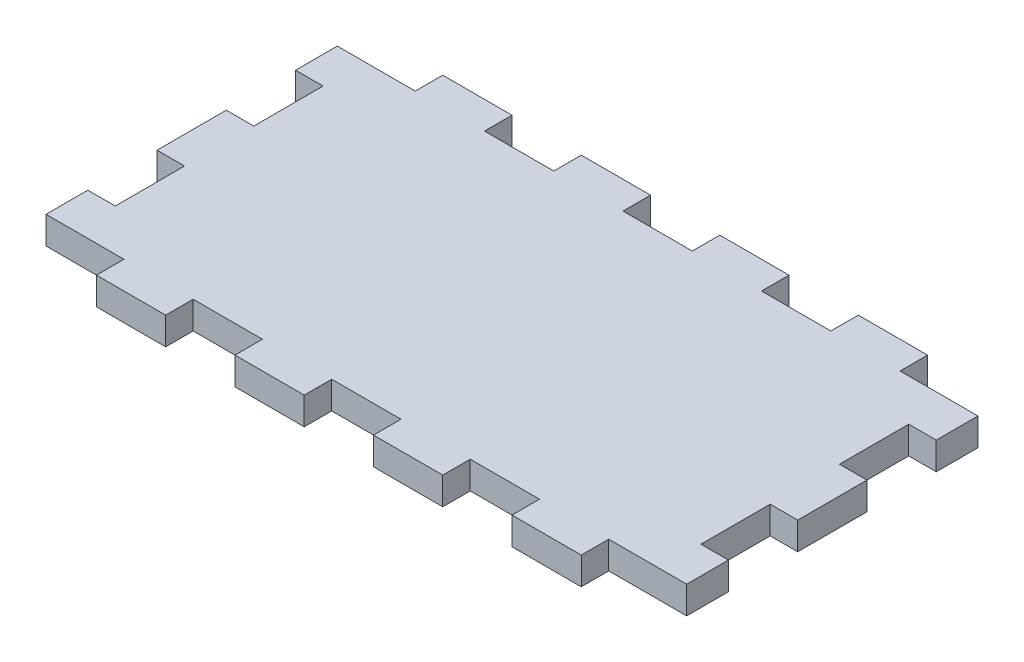
SolidWorks part; units mm, degrees
ref_plane "Front Plane" through (0, 0, 0) normal (0, 0, 1) x (1, 0, 0)
ref_plane "Top Plane" through (0, 0, 0) normal (0, 1, 0) x (1, 0, 0)
ref_plane "Right Plane" through (0, 0, 0) normal (1, 0, 0) x (0, 0, -1)
sketch "Sketch1" plane through (0, 0, 0) normal (0, 1, 0) x (1, 0, 0)
  line L1 (0, 0) -> (74, 0)
  line L2 (0, 0) -> (0, -40)
  line L3 (0, -40) -> (74, -40)
  line L4 (74, 0) -> (74, -40)
  dimension "D1" = 40
  dimension "D2" = 74
extrude "Boss-Extrude1" add sketch "Sketch1" along normal blind 3.175
sketch "Sketch2" plane through (0, 3.175, 0) normal (0, 1, 0) x (1, 0, 0)
  line L0 (37, 0) -> (37, -40) construction
  line L1 (74, 0) -> (0, 0) construction
  line L2 (0, -40) -> (74, -40) construction
  line L3 (0, -20) -> (74, -20) construction
  line L4 (0, 0) -> (0, -40) construction
  line L5 (74, -40) -> (74, 0) construction
  line L6 (9, 0) -> (9, -3.175)
  line L7 (33, 0) -> (41, 0)
  line L8 (0, -3.175) -> (9, -3.175)
  line L9 (33, -3.175) -> (41, -3.175)
  line L10 (41, 0) -> (41, -3.175)
  line L11 (49, 0) -> (57, 0)
  line L12 (49, 0) -> (49, -3.175)
  line L13 (49, -3.175) -> (57, -3.175)
  line L14 (57, 0) -> (57, -3.175)
  line L15 (74, 0) -> (65, 0)
  line L16 (74, 0) -> (74, -3.175)
  line L17 (74, -3.175) -> (65, -3.175)
  line L18 (65, 0) -> (65, -3.175)
  line L19 (0, 0) -> (0, -3.175)
  line L20 (0, 0) -> (9, 0)
  line L21 (17, 0) -> (17, -3.175)
  line L22 (25, -3.175) -> (17, -3.175)
  line L23 (25, 0) -> (25, -3.175)
  line L24 (25, 0) -> (17, 0)
  line L25 (33, 0) -> (33, -3.175)
  line L26 (33, -40) -> (33, -36.825)
  line L27 (25, -40) -> (17, -40)
  line L28 (25, -40) -> (25, -36.825)
  line L29 (25, -36.825) -> (17, -36.825)
  line L30 (17, -40) -> (17, -36.825)
  line L31 (0, -40) -> (9, -40)
  line L32 (0, -40) -> (0, -36.825)
  line L33 (65, -40) -> (65, -36.825)
  line L34 (74, -36.825) -> (65, -36.825)
  line L35 (74, -40) -> (74, -36.825)
  line L36 (74, -40) -> (65, -40)
  line L37 (57, -40) -> (57, -36.825)
  line L38 (49, -36.825) -> (57, -36.825)
  line L39 (49, -40) -> (49, -36.825)
  line L40 (49, -40) -> (57, -40)
  line L41 (41, -40) -> (41, -36.825)
  line L42 (33, -36.825) -> (41, -36.825)
  line L43 (0, -36.825) -> (9, -36.825)
  line L44 (33, -40) -> (41, -40)
  line L45 (9, -40) -> (9, -36.825)
  point P34 (37, -3.175)
  point P54 (37, -36.825)
  dimension "D1" = 4
  dimension "D2" = 3.175
  dimension "D3" = 3.175
  dimension "D4" = 8
  dimension "D5" = 8
  dimension "D6" = 3.175
  dimension "D7" = 8
extrude "Cut-Extrude1" cut sketch "Sketch2" against normal up to next
sketch "Sketch3" plane through (0, 3.175, 0) normal (0, 1, 0) x (1, 0, 0)
  line L0 (0, -20) -> (74, -20) construction
  line L1 (0, -3.175) -> (0, -36.825) construction
  line L2 (74, -36.825) -> (74, -3.175) construction
  line L3 (3.175, -24) -> (3.175, -32)
  line L4 (0, -16) -> (3.175, -16)
  line L5 (0, -16) -> (0, -8)
  line L6 (0, -8) -> (3.175, -8)
  line L7 (3.175, -16) -> (3.175, -8)
  line L8 (0, -32) -> (3.175, -32)
  line L9 (0, -24) -> (0, -32)
  line L10 (0, -24) -> (3.175, -24)
  line L11 (37, -3.175) -> (37, -36.825) construction
  line L12 (33, -3.175) -> (41, -3.175) construction
  line L13 (41, -36.825) -> (33, -36.825) construction
  line L14 (74, -24) -> (70.825, -24)
  line L15 (74, -24) -> (74, -32)
  line L16 (74, -32) -> (70.825, -32)
  line L17 (70.825, -16) -> (70.825, -8)
  line L18 (74, -8) -> (70.825, -8)
  line L19 (74, -16) -> (74, -8)
  line L20 (74, -16) -> (70.825, -16)
  line L21 (70.825, -24) -> (70.825, -32)
  dimension "D1" = 8
  dimension "D2" = 3.175
  dimension "D3" = 4
extrude "Cut-Extrude2" cut sketch "Sketch3" against normal up to next
